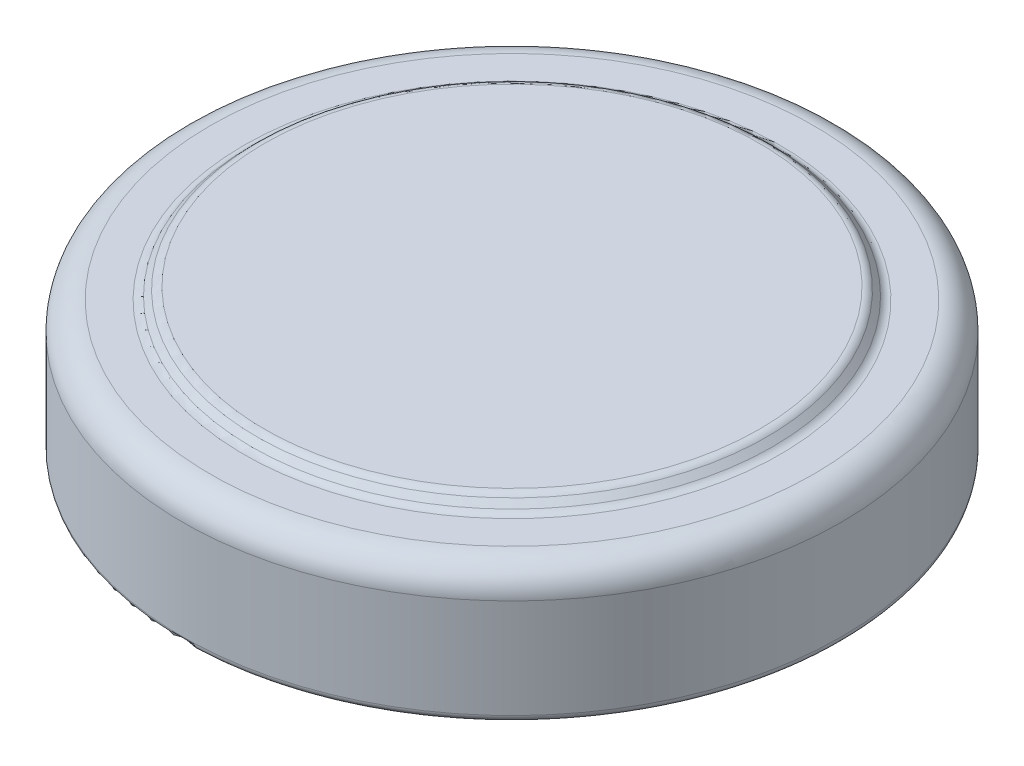
SolidWorks part; units mm, degrees
ref_plane "Front Plane" through (0, 0, 0) normal (0, 0, 1) x (1, 0, 0)
ref_plane "Top Plane" through (0, 0, 0) normal (0, 1, 0) x (1, 0, 0)
ref_plane "Right Plane" through (0, 0, 0) normal (1, 0, 0) x (0, 0, -1)
sketch "Sketch1" plane through (0, 0, 0) normal (0, 0, 1) x (1, 0, 0)
  line L0 (0, 0) -> (-4.65, 0)
  line L1 (-4.75, 0.1) -> (-4.75, 1.53)
  line L2 (-3.5679, 2.1) -> (0, 2.1)
  line L3 (0, 2.1) -> (0, 0)
  line L4 (-3.7561, 1.9739) -> (-3.6739, 2.0561)
  line L7 (-3.8621, 1.93) -> (-4.35, 1.93)
  arc A0 (-4.75, 1.53) -> (-4.35, 1.93) centre (-4.35, 1.53) cw
  arc A1 (-3.5679, 2.1) -> (-3.6739, 2.0561) centre (-3.5679, 1.95) ccw
  arc A2 (-3.8621, 1.93) -> (-3.7561, 1.9739) centre (-3.8621, 2.08) ccw
  arc A3 (-4.65, 0) -> (-4.75, 0.1) centre (-4.65, 0.1) cw
  point P9 (-4.75, 1.93)
  point P13 (-3.8, 1.93)
  point P17 (-4.75, 0)
  point P18 (-3.8, 1.93)
  point P20 (-3.8, 1.93)
  dimension "D6" = 0.4
  dimension "D7" = 0.15
  dimension "D8" = 0.1
  dimension "D1" = 4.75
  dimension "D2" = 2.1
  dimension "D3" = 3.8
  dimension "D4" = 1.93
  dimension "D5" = 45
revolve "Revolve1" add sketch "Sketch1" angle 360 about L3
sketch "Sketch2" plane through (0, 0, 0) normal (0, -1, 0) x (1, 0, 0)
  line L0 (0.25, 0.25) -> (2, 0.25)
  line L1 (-0.25, 2) -> (0.25, 2)
  line L2 (-0.25, 2) -> (-0.25, 0.25)
  line L3 (-0.25, -2) -> (0.25, -2)
  line L4 (0.25, 2) -> (0.25, 0.25)
  line L5 (-2, 0.25) -> (-0.25, 0.25)
  line L6 (-2, 0.25) -> (-2, -0.25)
  line L7 (-2, -0.25) -> (-0.25, -0.25)
  line L8 (2, 0.25) -> (2, -0.25)
  line L9 (0.25, -0.25) -> (2, -0.25)
  line L10 (0.25, -0.25) -> (0.25, -2)
  line L11 (-0.25, -0.25) -> (-0.25, -2)
  circle A0 centre (0, 0) radius 3.25 construction
  text T0 "                          SR69" font "Century Gothic" height 1
  dimension "D1" = 6.5
  dimension "D2" = 4
  dimension "D3" = 4
  dimension "D4" = 0.25
  dimension "D5" = 0.5
  dimension "D6" = 0.25
  dimension "D7" = 0.5
  dimension "D8" = 2
  dimension "D9" = 2
wrap "Wrap1" sketch "Sketch2" wrap type scribe source sketch "Sketch2" face at (-4.65, 0, 0)
